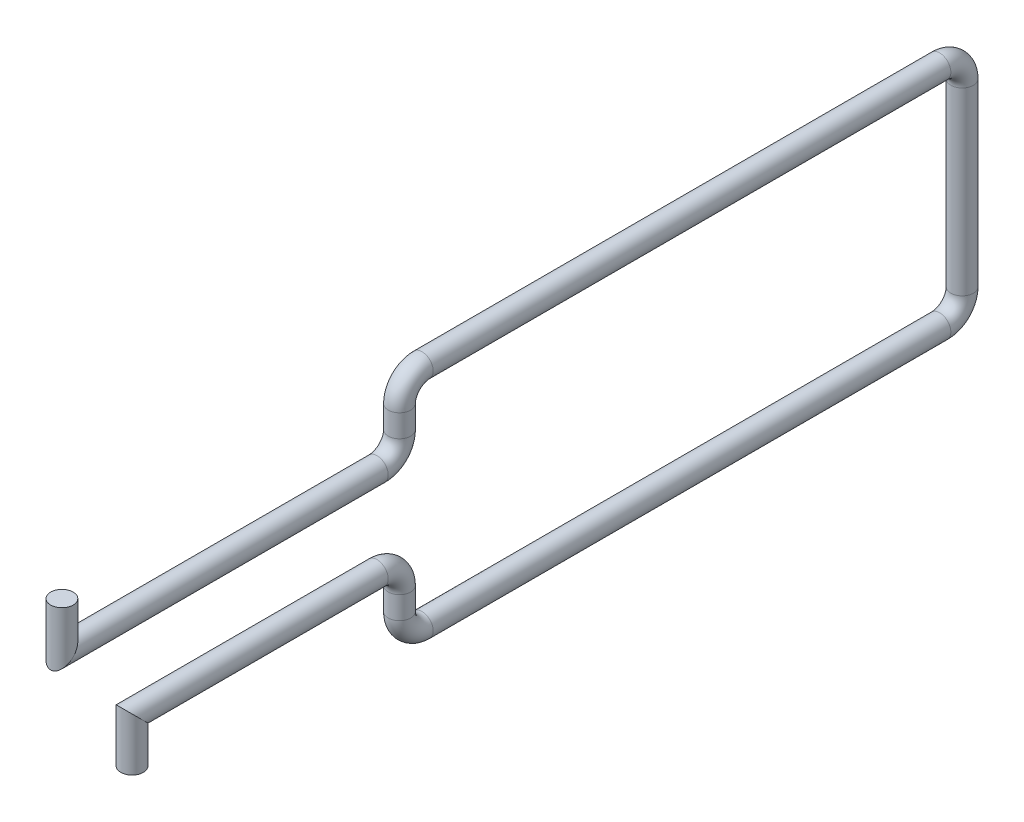
SolidWorks part; units mm, degrees
ref_plane "Vorne" through (0, 0, 0) normal (0, 0, 1) x (1, 0, 0)
ref_plane "Oben" through (0, 0, 0) normal (0, 1, 0) x (1, 0, 0)
ref_plane "Rechts" through (0, 0, 0) normal (1, 0, 0) x (0, 0, -1)
sketch "Skizze1" plane through (0, 0, 0) normal (1, 0, 0) x (0, 0, -1)
  line L0 (0, 4) -> (28, 4)
  line L1 (30, 6) -> (30, 8)
  line L2 (32, 10) -> (78, 10)
  line L3 (80, 8) -> (80, -8)
  line L4 (78, -10) -> (32, -10)
  line L5 (30, -8) -> (30, -6)
  line L6 (28, -4) -> (6.2349, -4)
  line L7 (0, 4) -> (0, 8)
  line L8 (6.2349, -4) -> (6.2349, -8)
  arc A0 (32, -10) -> (30, -8) centre (32, -8) cw
  arc A1 (30, -6) -> (28, -4) centre (28, -6) ccw
  arc A2 (28, 4) -> (30, 6) centre (28, 6) ccw
  arc A3 (30, 8) -> (32, 10) centre (32, 8) cw
  arc A4 (78, -10) -> (80, -8) centre (78, -8) ccw
  arc A5 (80, 8) -> (78, 10) centre (78, 8) ccw
  point P11 (30, -10)
  point P14 (30, -4)
  point P17 (30, 4)
  point P20 (30, 10)
  point P23 (80, -10)
  point P26 (80, 10)
  dimension "D10" = 2
  dimension "D1" = 4
  dimension "D2" = 30
  dimension "D3" = 50
  dimension "D4" = 20
  dimension "D5" = 6
  dimension "D6" = 6
  dimension "D8" = 50
  dimension "D11" = 4
  dimension "D12" = 4
ref_axis "Achse1" through (0, 0, -80.9) along (0, 0, 1)
ref_plane "Ebene1" through (0, 8, 0) normal (0, 1, 0) x (1, 0, 0)
sketch "Skizze5" plane through (0, 8, 0) normal (0, 1, 0) x (1, 0, 0)
  circle A0 centre (0, 0) radius 1
  dimension "D1" = 2
sweep "Austragung1" add profiles "Skizze5" path "Skizze1"
